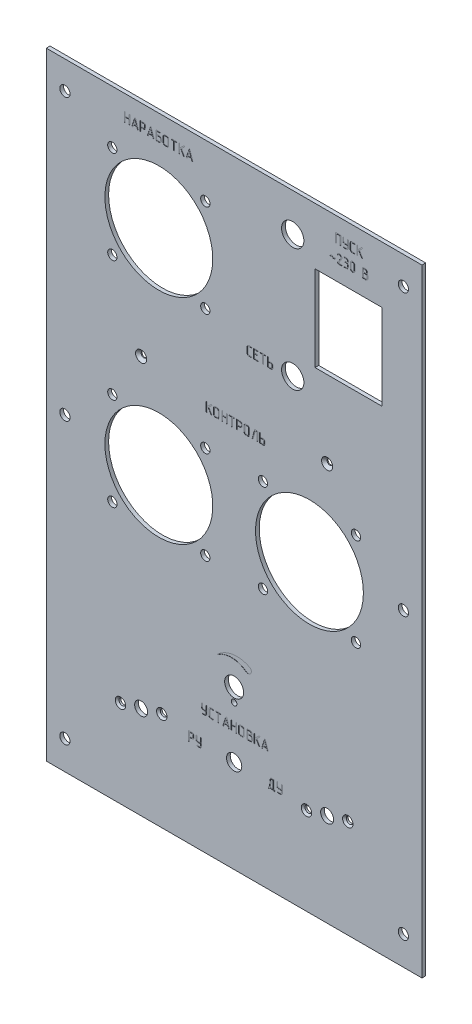
SolidWorks part; units mm, degrees
ref_plane "Спереди" through (0, 0, 0) normal (0, 0, 1) x (1, 0, 0)
ref_plane "Сверху" through (0, 0, 0) normal (0, 1, 0) x (1, 0, 0)
ref_plane "Справа" through (0, 0, 0) normal (1, 0, 0) x (0, 0, -1)
sketch "Эскиз1" plane through (0, 0, 0) normal (0, 0, 1) x (1, 0, 0)
  line L0 (0, 0) -> (41.8329, 0) construction
  line L1 (-101, -166) -> (101, -166)
  line L2 (-101, -166) -> (-101, 166)
  line L3 (-101, 166) -> (101, 166)
  line L4 (101, -166) -> (101, 166)
  line L5 (0, 0) -> (0, 25.0364) construction
  dimension "D1" = 332
  dimension "D2" = 202
extrude "Вытянуть1" add sketch "Эскиз1" along normal blind 2
sketch "Эскиз2" plane through (0, 0, 2) normal (0, 0, 1) x (1, 0, 0)
  line L0 (0, 179.4013) -> (0, -178.8924) construction
  line L1 (-115.1207, 0.2545) -> (145.9655, 0.2545) construction
  line L2 (101, 166) -> (-101, 166) construction
  line L3 (101, -166) -> (101, 166) construction
  line L4 (31.5, 79.5) -> (31.5, 145.5) construction
  line L5 (43.5, 89.5) -> (79.5, 89.5)
  line L6 (43.5, 89.5) -> (43.5, 135.5)
  line L7 (43.5, 135.5) -> (79.5, 135.5)
  line L8 (79.5, 89.5) -> (79.5, 135.5)
  circle A0 centre (91, 0.2545) radius 2.75
  circle A1 centre (91, 151) radius 2.75
  circle A2 centre (91, -150.4911) radius 2.75
  circle A3 centre (-91, -150.4911) radius 2.75
  circle A4 centre (-91, 151) radius 2.75
  circle A5 centre (-91, 0.2545) radius 2.75
  circle A6 centre (31.5, 145.5) radius 6
  circle A7 centre (31.5, 79.5) radius 6
  dimension "D1" = 15
  dimension "D2" = 5.5
  dimension "D3" = 10
  dimension "D4" = 10
  dimension "D9" = 66
  dimension "D11" = 12
  dimension "D5" = 46
  dimension "D6" = 36
  dimension "D7" = 30.5
  dimension "D8" = 21.5
  dimension "D10" = 10
  dimension "D12" = 12
extrude "Вырез-Вытянуть1" cut sketch "Эскиз2" against normal blind 10
sketch "Эскиз3" plane through (0, 0, 2) normal (0, 0, 1) x (1, 0, 0)
  line L0 (-40.5, 183.372) -> (-40.5, 70.433) construction
  line L1 (-85.9063, 112.5) -> (38.884, 112.5) construction
  line L2 (79.5, 135.5) -> (43.5, 135.5) construction
  line L3 (43.5, 89.5) -> (79.5, 89.5) construction
  line L4 (-125.9218, 55) -> (127.5386, 55) construction
  line L5 (0, -18.9064) -> (0, 87.5) construction
  circle A0 centre (-40.5, 112.5) radius 29
  circle A1 centre (-65.5, 137.5) radius 2.5
  circle A2 centre (-15.5, 137.5) radius 2.5
  circle A3 centre (-15.5, 87.5) radius 2.5
  circle A4 centre (-65.5, 87.5) radius 2.5
  circle A5 centre (31.5, 145.5) radius 6 construction
  circle A6 centre (-65.5, 22.5) radius 2.5
  circle A7 centre (-15.5, 22.5) radius 2.5
  circle A8 centre (-15.5, -27.5) radius 2.5
  circle A9 centre (-65.5, -27.5) radius 2.5
  circle A10 centre (-40.5, -2.5) radius 29
  circle A11 centre (40.5, -2.5) radius 29
  circle A12 centre (65.5, -27.5) radius 2.5
  circle A13 centre (15.5, -27.5) radius 2.5
  circle A14 centre (15.5, 22.5) radius 2.5
  circle A15 centre (65.5, 22.5) radius 2.5
  dimension "D1" = 50
  dimension "D2" = 50
  dimension "D4" = 58
  dimension "D5" = 5
  dimension "D3" = 72
  dimension "D6" = 57.5
extrude "Вырез-Вытянуть2" cut sketch "Эскиз3" against normal blind 10
sketch "Эскиз4" plane through (0, 0, 2) normal (0, 0, 1) x (1, 0, 0)
  line L0 (0, 0) -> (0, -137.6682) construction
  line L1 (-101, -166) -> (101, -166) construction
  circle A0 centre (0, -81) radius 5.1
  circle A1 centre (0, -88.2) radius 1.5
  circle A2 centre (0, -116) radius 4.1
  dimension "D1" = 10.2
  dimension "D2" = 3
  dimension "D3" = 7.2
  dimension "D4" = 35
  dimension "D5" = 8.2
  dimension "D6" = 50
extrude "Вырез-Вытянуть3" cut sketch "Эскиз4" against normal blind 10
sketch "Эскиз5" plane through (0, 0, 2) normal (0, 0, 1) x (1, 0, 0)
  line L0 (0, -116) -> (-74.1457, -116) construction
  line L1 (-50, -142.7776) -> (-50, -66.509) construction
  line L2 (-72.1213, -121.9129) -> (-23.3655, -108.8488) construction
  line L3 (-61.8152, -116) -> (-19.5437, -116) construction
  line L4 (32.0227, -120.817) -> (70.3149, -110.5566) construction
  line L5 (32.6665, -116) -> (65.1307, -116) construction
  line L6 (50, -116) -> (50, -88.1165) construction
  circle A2 centre (-50, -116) radius 3.5
  circle A3 centre (-61.1118, -118.9629) radius 1.8
  circle A4 centre (-38.8955, -113.01) radius 1.8
  circle A5 centre (0, -116) radius 4.1 construction
  circle A6 centre (50, -116) radius 3.5
  circle A7 centre (38.8919, -118.9764) radius 1.8
  circle A8 centre (61.1081, -113.0236) radius 1.8
  dimension "D4" = 7
  dimension "D5" = 3.6
  dimension "D6" = 50
  dimension "D10" = 50
  dimension "D11" = 3.6
  dimension "D12" = 7
  dimension "D1" = 23
  dimension "D2" = 11.5
  dimension "D3" = 15
  dimension "D7" = 15
  dimension "D8" = 23
  dimension "D9" = 11.5
extrude "Вырез-Вытянуть4" cut sketch "Эскиз5" against normal blind 10
chamfer "Фаска1" distance 1 angle 45 4 edges at (-59.3118, -118.9629, 2) (-37.0955, -113.01, 2) (62.9081, -113.0236, 2) (40.6919, -118.9764, 2)
sketch "Эскиз6" plane through (0, 0, 2) normal (0, 0, 1) x (1, 0, 0)
  line L0 (-118.3013, 48) -> (119.7769, 48) construction
  line L1 (101, 166) -> (-101, 166) construction
  line L2 (101, -166) -> (101, 166) construction
  circle A0 centre (-50, 48) radius 1.5
  circle A1 centre (50, 48) radius 1.5
  dimension "D2" = 100
  dimension "D3" = 51
  dimension "D4" = 3
  dimension "D1" = 118
extrude "Вырез-Вытянуть5" cut sketch "Эскиз6" against normal blind 10
sketch "Эскиз8" plane through (0, 0, 2) normal (0, 0, 1) x (1, 0, 0)
  line L0 (79.5, 135.5) -> (43.5, 135.5) construction
  circle A1 centre (31.5, 79.5) radius 6 construction
  text T0 " ПУСК\r\n~230 В" font "GOST type B" height 5
  text T1 "СЕТЬ" font "GOST type B" height 5
  dimension "D3" = 2.5
  dimension "D1" = 7.5
  dimension "D2" = 17.5
  dimension "D4" = 25
extrude "Вырез-Вытянуть6" cut sketch "Эскиз8" against normal blind 0.1
sketch "Эскиз9" plane through (0, 0, 2) normal (0, 0, 1) x (1, 0, 0)
  circle A0 centre (-40.5, 112.5) radius 29 construction
  text T0 "НАРАБОТКА" font "GOST type B" height 5
  dimension "D1" = 19
  dimension "D2" = 40
extrude "Вырез-Вытянуть7" cut sketch "Эскиз9" against normal blind 0.1
sketch "Эскиз10" plane through (0, 0, 2) normal (0, 0, 1) x (1, 0, 0)
  circle A0 centre (-40.5, -2.5) radius 29 construction
  text T0 "КОНТРОЛЬ" font "GOST type B" height 5
  dimension "D1" = 42
  dimension "D2" = 25
extrude "Вырез-Вытянуть8" cut sketch "Эскиз10" against normal blind 0.1
sketch "Эскиз11" plane through (0, 0, 2) normal (0, 0, 1) x (1, 0, 0)
  line L0 (0, -81) -> (0, -77.386) construction
  line L1 (-7.8779, -81) -> (10.8779, -81) construction
  arc A0 (6.3761, -70.6575) -> (-9.3333, -70.6251) centre (-1.5, -81) ccw
  arc A1 (8.2803, -67.6199) -> (-9.3333, -70.6251) centre (1.5, -81) ccw
  arc A2 (6.3761, -70.6575) -> (8.2803, -67.6199) centre (7.4667, -69.2255) ccw
  dimension "D3" = 26
  dimension "D4" = 30
  dimension "D5" = 3.6
  dimension "D1" = 1.5
  dimension "D2" = 3
extrude "Вырез-Вытянуть9" cut sketch "Эскиз11" against normal blind 0.1
sketch "Эскиз12" plane through (0, 0, 2) normal (0, 0, 1) x (1, 0, 0)
  circle A0 centre (0, -116) radius 4.1 construction
  text T0 "УСТАНОВКА" font "GOST type B" height 5
  text T1 "РУ" font "GOST type B" height 5
  text T2 "ДУ" font "GOST type B" height 5
  dimension "D1" = 14
  dimension "D3" = 2.5
  dimension "D4" = 25
  dimension "D6" = 18
  dimension "D2" = 18
  dimension "D5" = 2.5
extrude "Вырез-Вытянуть10" cut sketch "Эскиз12" against normal blind 0.1
chamfer "Фаска2" distance 1.5 angle 45 2 edges at (-48.5, 48, 2) (51.5, 48, 2)
